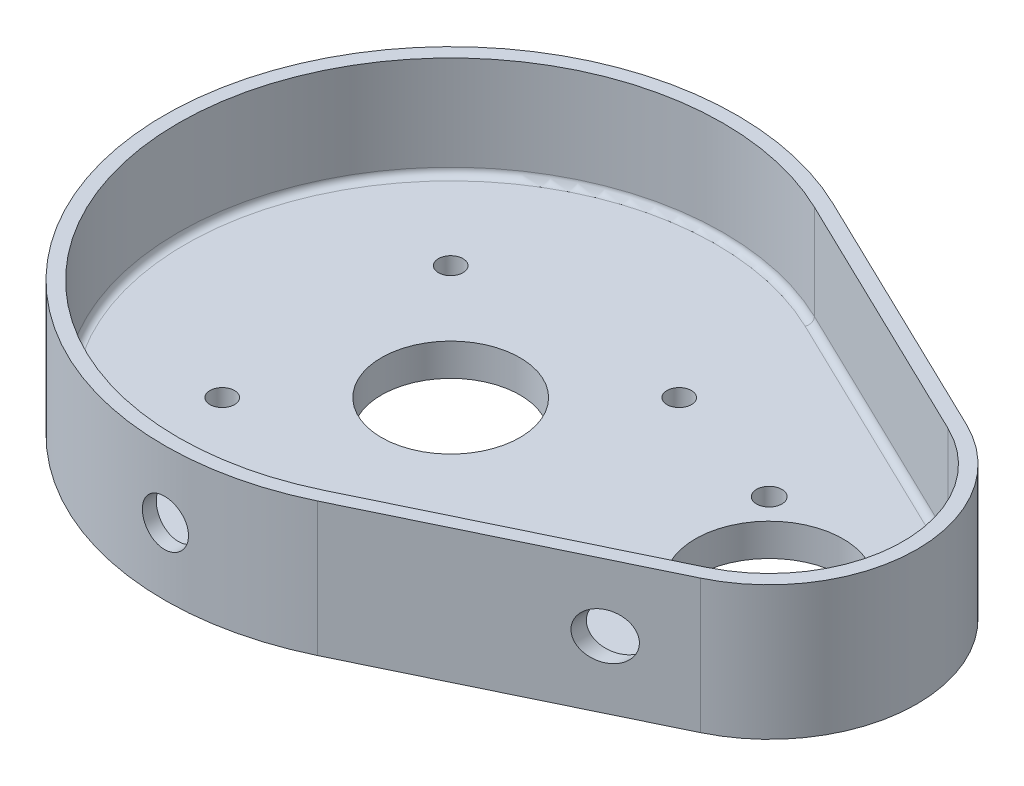
SolidWorks part; units mm, degrees
ref_plane "Front Plane" through (0, 0, 0) normal (0, 0, 1) x (1, 0, 0)
ref_plane "Top Plane" through (0, 0, 0) normal (0, 1, 0) x (1, 0, 0)
ref_plane "Right Plane" through (0, 0, 0) normal (1, 0, 0) x (0, 0, -1)
sketch "Sketch1" plane through (0, 0, 0) normal (0, 1, 0) x (1, 0, 0)
  line L0 (69, 0) -> (0, 0) construction
  line L1 (82.913, -28.8171) -> (26.9565, -55.8332)
  line L2 (82.913, 28.8171) -> (26.9565, 55.8332)
  circle A0 centre (0, 0) radius 15
  circle A1 centre (69, 0) radius 16
  arc A2 (26.9565, 55.8332) -> (26.9565, -55.8332) centre (0, 0) ccw
  arc A3 (82.913, -28.8171) -> (82.913, 28.8171) centre (69, 0) ccw
  dimension "D2" = 30
  dimension "D3" = 32
  dimension "D4" = 32
  dimension "D5" = 62
  dimension "D1" = 69
extrude "Boss-Extrude1" add sketch "Sketch1" along normal blind 7
sketch "Sketch3" plane through (0, 7, 0) normal (0, 1, 0) x (1, 0, 0)
  line L4 (81.6087, 26.1155) -> (25.6522, 53.1316)
  line L5 (25.6522, -53.1316) -> (81.6087, -26.1155)
  line L6 (81.6087, 26.1155) -> (25.6522, 53.1316)
  line L7 (25.6522, -53.1316) -> (81.6087, -26.1155)
  line L8 (82.913, 28.8171) -> (26.9565, 55.8332)
  line L9 (26.9565, -55.8332) -> (82.913, -28.8171)
  line L10 (82.913, 28.8171) -> (26.9565, 55.8332)
  line L11 (26.9565, -55.8332) -> (82.913, -28.8171)
  arc A4 (81.6087, -26.1155) -> (81.6087, 26.1155) centre (69, 0) ccw
  arc A5 (25.6522, 53.1316) -> (25.6522, -53.1316) centre (0, 0) ccw
  arc A6 (81.6087, -26.1155) -> (81.6087, 26.1155) centre (69, 0) ccw
  arc A7 (25.6522, 53.1316) -> (25.6522, -53.1316) centre (0, 0) ccw
  arc A8 (82.913, -28.8171) -> (82.913, 28.8171) centre (69, 0) ccw
  arc A9 (26.9565, 55.8332) -> (26.9565, -55.8332) centre (0, 0) ccw
  arc A10 (82.913, -28.8171) -> (82.913, 28.8171) centre (69, 0) ccw
  arc A11 (26.9565, 55.8332) -> (26.9565, -55.8332) centre (0, 0) ccw
  dimension "D1" = 3
  dimension "D2" = 0
extrude "Boss-Extrude2" add sketch "Sketch3" along normal blind 22
sketch "Sketch4" plane through (0, 0, 0) normal (0, -1, 0) x (1, 0, 0)
  circle A4 centre (24.7487, -24.7487) radius 2.655
  circle A5 centre (-24.7487, -24.7487) radius 2.655
  circle A6 centre (-24.7487, 24.7487) radius 2.655
  circle A7 centre (24.7487, 24.7487) radius 2.655
extrude "Cut-Extrude1" cut sketch "Sketch4" against normal up to next
sketch "Sketch5" plane through (0, 7, 0) normal (0, 1, 0) x (1, 0, 0)
  line L0 (69, 0) -> (46.5, 0) construction
  line L1 (69, 0) -> (53.0901, 15.9099) construction
  circle A0 centre (69, 0) radius 22.5 construction
  circle A1 centre (53.0901, 15.9099) radius 2.75
  circle A2 centre (84.9099, 15.9099) radius 2.75
  circle A3 centre (84.9099, -15.9099) radius 2.75
  circle A4 centre (53.0901, -15.9099) radius 2.75
  point P15 (69, 0)
  dimension "D1" = 45
  dimension "D3" = 5.5
  dimension "D2" = 45
  dimension "D4" = 4
extrude "Cut-Extrude2" cut sketch "Sketch5" against normal blind 15
fillet "Fillet1" radius 1.5 4 edges at (98, 7, 0) (53.6304, 7, 39.6236) (-59, 7, 0) (53.6304, 7, -39.6236)
sketch "Sketch7" plane through (0, 0, 0) normal (0, 0, 1) x (1, 0, 0)
  line L0 (-15, 0) -> (15, 0) construction
  line L1 (53, 0) -> (85, 0) construction
  line L2 (53, 0) -> (85, 0) construction
  line L3 (-15, 0) -> (15, 0) construction
  line L4 (0, 0) -> (0, 29) construction
  line L5 (25.6522, 29) -> (-59, 29) construction
  line L6 (69, 0) -> (69, 29) construction
  line L7 (26.9565, 29) -> (82.913, 29) construction
  circle A0 centre (0, 14.5) radius 5
  circle A1 centre (69, 14.5) radius 5
  dimension "D1" = 10
extrude "Cut-Extrude3" cut sketch "Sketch7" along normal up to next
